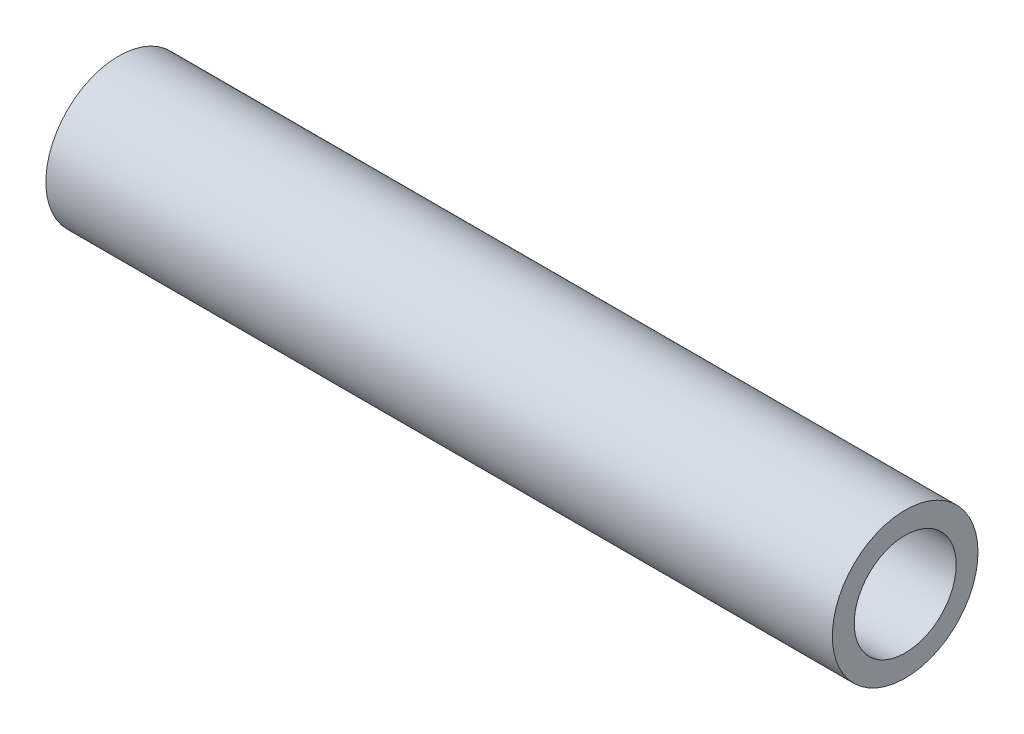
SolidWorks part; units mm, degrees
ref_plane "Alzado" through (0, 0, 0) normal (0, 0, 1) x (1, 0, 0)
ref_plane "Planta" through (0, 0, 0) normal (0, 1, 0) x (1, 0, 0)
ref_plane "Vista lateral" through (0, 0, 0) normal (1, 0, 0) x (0, 0, -1)
sketch "Croquis1" plane through (0, 0, 0) normal (1, 0, 0) x (0, 0, -1)
  circle A0 centre (0, 0) radius 2.5
  circle A1 centre (0, 0) radius 1.75
extrude "Saliente-Extruir1" add sketch "Croquis1" along normal blind 13.5 and the other way blind 13.5
